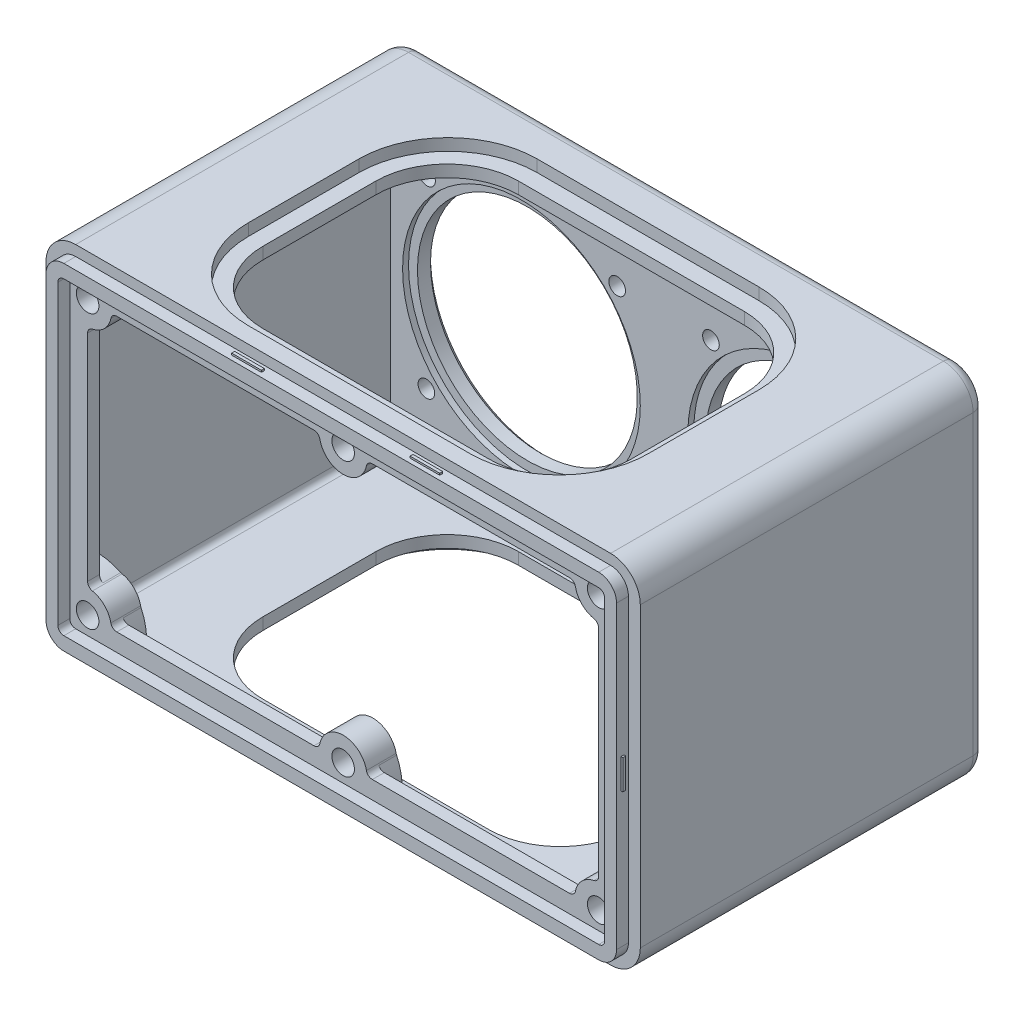
SolidWorks part; units mm, degrees
ref_plane "前视基准面" through (0, 0, 0) normal (0, 0, 1) x (1, 0, 0)
ref_plane "上视基准面" through (0, 0, 0) normal (0, 1, 0) x (1, 0, 0)
ref_plane "右视基准面" through (0, 0, 0) normal (1, 0, 0) x (0, 0, -1)
other "Configuration Table"
sketch "草图1" plane through (0, 0, 0) normal (0, 0, 1) x (1, 0, 0)
  line L0 (0, 0.156) -> (-70, 0.156) construction
  line L6 (-50, 30) -> (50, 30)
  line L11 (-50, 30) -> (-50, -30)
  line L12 (-50, -30) -> (50, -30)
  line L13 (50, 30) -> (50, -30)
  line L22 (-50, 30) -> (50, -30) construction
  line L23 (-50, -30) -> (50, 30) construction
  point P0 (0, 0)
  point P1 (0, 0)
  point P18 (0, 0)
  point P41 (0, 0)
  dimension "D1" = 100
  dimension "D2" = 60
extrude "凸台-拉伸2" add sketch "草图1" along normal blind 60
fillet "圆角1" radius 5 4 edges at (50, -30, 30) (50, 30, 30) (-50, 30, 30) (-50, -30, 30)
shell "抽壳2" thickness 4 removed face at (0, 0, 60)
fillet "圆角3" radius 2 8 edges at (48.5355, 28.5355, 0) (50, 0, 0) (48.5355, -28.5355, 0) (0, -30, 0) (-48.5355, -28.5355, 0) (-50, 0, 0) (-48.5355, 28.5355, 0) (0, 30, 0)
sketch "草图2" plane through (0, 0, 0) normal (0, 0, -1) x (-1, 0, 0)
  line L0 (0, 0) -> (-48, 0) construction
  circle A0 centre (-24, 0) radius 18
  circle A1 centre (24, 0) radius 18.5
  dimension "D1" = 36
  dimension "D2" = 37
  dimension "D3" = 24
  dimension "D4" = 24
extrude "切除-拉伸1" cut sketch "草图2" against normal up to next
sketch "草图3" plane through (0, -30, 0) normal (0, -1, 0) x (1, 0, 0)
  line L0 (0, 0) -> (0, 60) construction
  line L1 (-45, 60) -> (45, 60) construction
  line L2 (45, 31) -> (-45, 31) construction
  line L3 (45, 2) -> (45, 60) construction
  line L4 (-45, 60) -> (-45, 2) construction
  line L6 (19, 52.5) -> (-19, 52.5)
  line L7 (31, 40.5) -> (31, 21.5)
  line L8 (19, 9.5) -> (-19, 9.5)
  line L9 (-31, 40.5) -> (-31, 21.5)
  line L10 (31, 52.5) -> (-31, 9.5) construction
  line L11 (31, 9.5) -> (-31, 52.5) construction
  arc A0 (19, 9.5) -> (31, 21.5) centre (19, 21.5) ccw
  arc A1 (-31, 21.5) -> (-19, 9.5) centre (-19, 21.5) ccw
  arc A2 (-31, 40.5) -> (-19, 52.5) centre (-19, 40.5) cw
  arc A3 (19, 52.5) -> (31, 40.5) centre (19, 40.5) cw
  point P11 (0, 31)
  dimension "D1" = 12
extrude "切除-拉伸2" cut sketch "草图3" against normal up to surface (60 mm away) up to face at (0, 30, 31)
sketch "草图4" plane through (0, -30, 0) normal (0, -1, 0) x (1, 0, 0)
  line L0 (-45, 2) -> (45, 2) construction
  line L2 (0, 60) -> (0, 2) construction
  line L3 (18.65, 55.3) -> (-18.65, 55.3)
  line L4 (33.65, 40.3) -> (33.65, 21.7)
  line L5 (18.65, 6.7) -> (-18.65, 6.7)
  line L6 (-33.65, 40.3) -> (-33.65, 21.7)
  line L7 (33.65, 55.3) -> (-33.65, 6.7) construction
  line L8 (33.65, 6.7) -> (-33.65, 55.3) construction
  line L9 (-45, 60) -> (45, 60) construction
  arc A0 (-18.65, 6.7) -> (-33.65, 21.7) centre (-18.65, 21.7) cw
  arc A1 (-33.65, 40.3) -> (-18.65, 55.3) centre (-18.65, 40.3) cw
  arc A2 (33.65, 21.7) -> (18.65, 6.7) centre (18.65, 21.7) cw
  arc A3 (18.65, 55.3) -> (33.65, 40.3) centre (18.65, 40.3) cw
  point P5 (0, 31)
  point P26 (0, 31)
  dimension "D1" = 15
  dimension "D2" = 48.6
  dimension "D3" = 67.3
extrude "切除-拉伸3" cut sketch "草图4" against normal blind 2
sketch "草图5" plane through (0, 30, 0) normal (0, 1, 0) x (1, 0, 0)
  line L0 (-33.65, -40.3) -> (-33.65, -21.7) construction
  line L1 (18.65, -6.7) -> (-18.65, -6.7) construction
  line L2 (18.65, -55.3) -> (-18.65, -55.3) construction
  line L3 (33.65, -40.3) -> (33.65, -21.7) construction
  line L4 (-33.65, -40.3) -> (-33.65, -21.7)
  line L5 (18.65, -6.7) -> (-18.65, -6.7)
  line L6 (18.65, -55.3) -> (-18.65, -55.3)
  line L7 (33.65, -40.3) -> (33.65, -21.7)
  arc A0 (-33.65, -40.3) -> (-18.65, -55.3) centre (-18.65, -40.3) ccw construction
  arc A1 (-18.65, -6.7) -> (-33.65, -21.7) centre (-18.65, -21.7) ccw construction
  arc A2 (18.65, -55.3) -> (33.65, -40.3) centre (18.65, -40.3) ccw construction
  arc A3 (33.65, -21.7) -> (18.65, -6.7) centre (18.65, -21.7) ccw construction
  arc A4 (-33.65, -40.3) -> (-18.65, -55.3) centre (-18.65, -40.3) ccw
  arc A5 (-18.65, -6.7) -> (-33.65, -21.7) centre (-18.65, -21.7) ccw
  arc A6 (18.65, -55.3) -> (33.65, -40.3) centre (18.65, -40.3) ccw
  arc A7 (33.65, -21.7) -> (18.65, -6.7) centre (18.65, -21.7) ccw
extrude "切除-拉伸4" cut sketch "草图5" against normal blind 2
sketch "草图6" plane through (0, 0, 0) normal (0, 0, -1) x (-1, 0, 0)
  line L1 (200000, 0) -> (-200048, 0) construction
  line L2 (-40, -15.5) -> (-8, -15.5) construction
  line L3 (-39.8873, 15.5) -> (-7.8873, 15.5) construction
  line L4 (0, 0) -> (0, -28) construction
  line L5 (-24, 0) -> (-24, -15.5) construction
  circle A0 centre (-39.8873, 15.5) radius 1.4
  circle A1 centre (-40, -15.5) radius 1.4
  circle A3 centre (-8, -15.5) radius 1.4
  circle A4 centre (-7.8873, 15.5) radius 1.4
  circle A8 centre (8, -15.5) radius 1.4
  circle A9 centre (40, -15.5) radius 1.4
  circle A10 centre (7.8873, 15.5) radius 1.4
  circle A11 centre (39.8873, 15.5) radius 1.4
  point P16 (-24, -15.5)
  dimension "D1" = 2.8
  dimension "D5" = 2.8
  dimension "D6" = 2.8
  dimension "D7" = 2.8
  dimension "D2" = 31
  dimension "D3" = 32
  dimension "D4" = 32
  dimension "D8" = 15.5
extrude "切除-拉伸5" cut sketch "草图6" against normal up to next
sketch "草图7" plane through (0, 0, 60) normal (0, 0, 1) x (1, 0, 0)
  line L1 (45, 28.25) -> (-45, 28.25)
  line L2 (48, 25.25) -> (48, -25.25)
  line L3 (45, -28.25) -> (-45, -28.25)
  line L4 (-48, 25.25) -> (-48, -25.25)
  line L5 (48, 28.25) -> (-48, -28.25) construction
  line L6 (48, -28.25) -> (-48, 28.25) construction
  arc A0 (45, -28.25) -> (48, -25.25) centre (45, -25.25) ccw
  arc A1 (-48, -25.25) -> (-45, -28.25) centre (-45, -25.25) ccw
  arc A2 (-45, 28.25) -> (-48, 25.25) centre (-45, 25.25) ccw
  arc A3 (45, 28.25) -> (48, 25.25) centre (45, 25.25) cw
  point P0 (0, 0)
  dimension "D3" = 3
  dimension "D1" = 56.5
  dimension "D2" = 96
extrude "切除-拉伸6" cut sketch "草图7" against normal blind 2 flip side to cut
sketch "草图8" plane through (0, -28.25, 0) normal (0, -1, 0) x (1, 0, 0)
  line L0 (-45, 58) -> (-45, 60) construction
  line L1 (-45, 59) -> (45, 59) construction
  line L2 (45, 58) -> (45, 60) construction
  line L4 (12.5, 59.25) -> (17.5, 59.25)
  line L5 (12.5, 59.25) -> (12.5, 58.75)
  line L6 (12.5, 58.75) -> (17.5, 58.75)
  line L7 (17.5, 59.25) -> (17.5, 58.75)
  line L8 (12.5, 59.25) -> (17.5, 58.75) construction
  line L9 (12.5, 58.75) -> (17.5, 59.25) construction
  line L22 (-17.5, 59.25) -> (-12.5, 59.25)
  line L23 (-17.5, 59.25) -> (-17.5, 58.75)
  line L24 (-17.5, 58.75) -> (-12.5, 58.75)
  line L25 (-12.5, 59.25) -> (-12.5, 58.75)
  line L26 (-17.5, 59.25) -> (-12.5, 58.75) construction
  line L27 (-17.5, 58.75) -> (-12.5, 59.25) construction
  point P6 (15, 59)
  point P12 (-15, 59)
  dimension "D1" = 30
  dimension "D2" = 0.5
  dimension "D3" = 5
  dimension "D4" = 60
extrude "凸台-拉伸3" add sketch "草图8" along normal blind 0.3
sketch "草图9" plane through (0, 28.25, 0) normal (0, 1, 0) x (1, 0, 0)
  line L0 (-17.5, -59.25) -> (-12.5, -59.25) construction
  line L1 (-12.5, -59.25) -> (-12.5, -58.75) construction
  line L2 (-17.5, -58.75) -> (-12.5, -58.75) construction
  line L3 (-17.5, -59.25) -> (-17.5, -58.75) construction
  line L4 (12.5, -59.25) -> (12.5, -58.75) construction
  line L5 (17.5, -59.25) -> (17.5, -58.75) construction
  line L6 (12.5, -58.75) -> (17.5, -58.75) construction
  line L7 (12.5, -59.25) -> (17.5, -59.25) construction
  line L8 (-17.5, -59.25) -> (-12.5, -59.25)
  line L9 (-12.5, -59.25) -> (-12.5, -58.75)
  line L10 (-17.5, -58.75) -> (-12.5, -58.75)
  line L11 (-17.5, -59.25) -> (-17.5, -58.75)
  line L12 (12.5, -59.25) -> (12.5, -58.75)
  line L13 (17.5, -59.25) -> (17.5, -58.75)
  line L14 (12.5, -58.75) -> (17.5, -58.75)
  line L15 (12.5, -59.25) -> (17.5, -59.25)
extrude "凸台-拉伸4" add sketch "草图9" along normal blind 0.3
sketch "草图10" plane through (48, 0, 0) normal (1, 0, 0) x (0, 0, -1)
  line L0 (-59, -25.25) -> (-59, 25.25) construction
  line L1 (-59.25, -2.5) -> (-58.75, -2.5)
  line L2 (-59.25, -2.5) -> (-59.25, 2.5)
  line L3 (-59.25, 2.5) -> (-58.75, 2.5)
  line L4 (-58.75, -2.5) -> (-58.75, 2.5)
  line L5 (-59.25, -2.5) -> (-58.75, 2.5) construction
  line L6 (-59.25, 2.5) -> (-58.75, -2.5) construction
  line L7 (-58, -25.25) -> (-60, -25.25) construction
  line L8 (-58, 25.25) -> (-60, 25.25) construction
  point P0 (-59, 0)
  point P11 (-59, 0)
extrude "凸台-拉伸5" add sketch "草图10" along normal blind 0.3
sketch "草图11" plane through (-48, 0, 0) normal (-1, 0, 0) x (0, 0, 1)
  line L0 (59.25, -2.5) -> (58.75, -2.5) construction
  line L1 (59.25, -2.5) -> (59.25, 2.5) construction
  line L2 (59.25, 2.5) -> (58.75, 2.5) construction
  line L3 (58.75, -2.5) -> (58.75, 2.5) construction
  line L4 (59.25, -2.5) -> (58.75, -2.5)
  line L5 (59.25, -2.5) -> (59.25, 2.5)
  line L6 (59.25, 2.5) -> (58.75, 2.5)
  line L7 (58.75, -2.5) -> (58.75, 2.5)
extrude "凸台-拉伸6" add sketch "草图11" along normal blind 0.3
sketch "草图12" plane through (0, 0, 0) normal (0, 0, -1) x (-1, 0, 0)
  line L6 (0, 0) -> (0, -28.25) construction
sketch "草图13" plane through (0, 0, 4) normal (0, 0, 1) x (1, 0, 0)
  line L0 (0, 200000) -> (0, -200028.25) construction
  line L1 (0, 200000) -> (0, -200028.25)
  circle A0 centre (24, 0) radius 20
  circle A1 centre (-24, 0) radius 20
  dimension "D1" = 40
extrude "切除-拉伸8" cut sketch "草图13" against normal blind 1
sketch "草图14" plane through (0, 0, 58) normal (0, 0, 1) x (1, 0, 0)
  line L0 (0, 200000) -> (0, -200028.25) construction
  line L1 (45, 26) -> (-45, 26)
  line L2 (46, 25) -> (46, -25)
  line L3 (45, -26) -> (-45, -26)
  line L4 (-46, 25) -> (-46, -25)
  line L5 (46, 26) -> (-46, -26) construction
  line L6 (46, -26) -> (-46, 26) construction
  line L10 (-200000, 0) -> (200048, 0) construction
  line L11 (-200000, 0) -> (200048, 0)
  line L12 (0, 200000) -> (0, -200028.25)
  line L13 (43, 23) -> (-43, 23)
  line L14 (43, 23) -> (43, -23)
  line L15 (43, -23) -> (-43, -23)
  line L16 (-43, 23) -> (-43, -23)
  line L17 (43, 23) -> (-43, -23) construction
  line L18 (43, -23) -> (-43, 23) construction
  circle A0 centre (43, 23) radius 1.9
  circle A1 centre (0, 23) radius 1.9
  arc A6 (-45, 26) -> (-46, 25) centre (-45, 25) ccw
  arc A7 (-46, -25) -> (-45, -26) centre (-45, -25) ccw
  arc A8 (45, -26) -> (46, -25) centre (45, -25) ccw
  arc A9 (45, 26) -> (46, 25) centre (45, 25) cw
  circle A10 centre (-43, 23) radius 1.9
  circle A11 centre (-43, -23) radius 1.9
  circle A12 centre (0, -23) radius 1.9
  circle A13 centre (43, -23) radius 1.9
  circle A14 centre (43, 23) radius 4
  circle A15 centre (0, 23) radius 4
  circle A16 centre (-43, 23) radius 4
  circle A17 centre (-43, -23) radius 4
  circle A18 centre (0, -23) radius 4
  circle A19 centre (43, -23) radius 4
  point P0 (0, 0)
  point P5 (0, 0)
  point P23 (0, 0)
  dimension "D5" = 3
  dimension "D3" = 3.8
  dimension "D6" = 3.8
  dimension "D8" = 1
  dimension "D9" = 8
  dimension "D10" = 8
  dimension "D1" = 52
  dimension "D2" = 92
  dimension "D4" = 3
  dimension "D7" = 3
sketch "草图16" plane through (0, 0, 58) normal (0, 0, 1) x (1, 0, 0)
  line L0 (45, 26) -> (-45, 26) construction
  line L1 (-46, 25) -> (-46, -25) construction
  line L2 (46, 25) -> (46, -25) construction
  line L3 (45, -26) -> (-45, -26) construction
  line L4 (43, 23) -> (-43, 23) construction
  line L5 (43, 23) -> (43, -23) construction
  line L6 (43, -23) -> (-43, -23) construction
  line L7 (-43, 23) -> (-43, -23) construction
  line L8 (45, 26) -> (-45, 26)
  line L9 (-46, 25) -> (-46, -25)
  line L10 (46, 25) -> (46, -25)
  line L11 (45, -26) -> (-45, -26)
  line L12 (38.0883, 23) -> (4.9117, 23)
  line L13 (43, 18.0883) -> (43, -18.0883)
  line L14 (38.0883, -23) -> (4.9117, -23)
  line L15 (-43, 18.0883) -> (-43, -18.0883)
  line L16 (-4.9117, 23) -> (-38.0883, 23)
  line L17 (-4.9117, -23) -> (-38.0883, -23)
  arc A0 (-46, -25) -> (-45, -26) centre (-45, -25) ccw construction
  arc A1 (-45, 26) -> (-46, 25) centre (-45, 25) ccw construction
  arc A2 (46, 25) -> (45, 26) centre (45, 25) ccw construction
  arc A3 (45, -26) -> (46, -25) centre (45, -25) ccw construction
  circle A4 centre (43, -23) radius 4 construction
  circle A5 centre (43, 23) radius 4 construction
  circle A6 centre (-43, -23) radius 4 construction
  circle A7 centre (-43, 23) radius 4 construction
  arc A8 (-46, -25) -> (-45, -26) centre (-45, -25) ccw
  arc A9 (-45, 26) -> (-46, 25) centre (-45, 25) ccw
  arc A10 (46, 25) -> (45, 26) centre (45, 25) ccw
  arc A11 (45, -26) -> (46, -25) centre (45, -25) ccw
  arc A12 (42.19, -19.0829) -> (39.0829, -22.19) centre (43, -23) ccw
  arc A13 (39.0829, 22.19) -> (42.19, 19.0829) centre (43, 23) ccw
  arc A14 (-39.0829, -22.19) -> (-42.19, -19.0829) centre (-43, -23) ccw
  arc A15 (-42.19, 19.0829) -> (-39.0829, 22.19) centre (-43, 23) ccw
  arc A16 (-38.0883, -23) -> (-39.0829, -22.19) centre (-38.0883, -21.9844) cw
  arc A17 (-43, -18.0883) -> (-42.19, -19.0829) centre (-41.9844, -18.0883) ccw
  arc A18 (-43, 18.0883) -> (-42.19, 19.0829) centre (-41.9844, 18.0883) cw
  arc A19 (-39.0829, 22.19) -> (-38.0883, 23) centre (-38.0883, 21.9844) cw
  arc A20 (38.0883, -23) -> (39.0829, -22.19) centre (38.0883, -21.9844) ccw
  arc A21 (42.19, -19.0829) -> (43, -18.0883) centre (41.9844, -18.0883) ccw
  arc A22 (38.0883, 23) -> (39.0829, 22.19) centre (38.0883, 21.9844) cw
  arc A23 (42.19, 19.0829) -> (43, 18.0883) centre (41.9844, 18.0883) cw
  circle A24 centre (0, -23) radius 4 construction
  circle A25 centre (0, 23) radius 4 construction
  arc A26 (3.9171, -22.19) -> (-3.9171, -22.19) centre (0, -23) ccw
  arc A27 (-3.9171, 22.19) -> (3.9171, 22.19) centre (0, 23) ccw
  arc A28 (-4.9117, -23) -> (-3.9171, -22.19) centre (-4.9117, -21.9844) ccw
  arc A29 (4.9117, -23) -> (3.9171, -22.19) centre (4.9117, -21.9844) cw
  arc A30 (-4.9117, 23) -> (-3.9171, 22.19) centre (-4.9117, 21.9844) cw
  arc A31 (4.9117, 23) -> (3.9171, 22.19) centre (4.9117, 21.9844) ccw
  point P58 (-4, -23)
  point P63 (-4, 23)
  dimension "D1" = 1.0156
  dimension "D2" = 1.0156
extrude "凸台-拉伸7" add sketch "草图16" against normal blind 2
sketch "草图19" plane through (0, 0, 56) normal (0, 0, -1) x (-1, 0, 0)
  line L0 (-43, 23) -> (-43, -23) construction
  line L1 (-43, -23) -> (43, -23) construction
  line L2 (43, 23) -> (43, -23) construction
  line L3 (-43, 23) -> (43, 23) construction
  line L4 (-43, 23) -> (-43, 18.0883)
  line L5 (-43, -23) -> (-38.0883, -23)
  line L6 (43, 23) -> (43, 18.0883)
  line L7 (-43, 23) -> (-38.0883, 23)
  line L8 (-4.9117, -23) -> (4.9117, -23)
  line L9 (-43, -18.0883) -> (-43, -23)
  line L10 (-4.9117, 23) -> (4.9117, 23)
  line L11 (38.0883, -23) -> (43, -23)
  line L12 (43, -18.0883) -> (43, -23)
  line L13 (38.0883, 23) -> (43, 23)
  arc A0 (39.0829, 22.19) -> (38.0883, 23) centre (38.0883, 21.9844) ccw construction
  arc A1 (43, 18.0883) -> (42.19, 19.0829) centre (41.9844, 18.0883) ccw construction
  arc A2 (42.19, -19.0829) -> (43, -18.0883) centre (41.9844, -18.0883) ccw construction
  arc A3 (38.0883, -23) -> (39.0829, -22.19) centre (38.0883, -21.9844) ccw construction
  arc A4 (-4.9117, -23) -> (-3.9171, -22.19) centre (-4.9117, -21.9844) ccw construction
  arc A5 (3.9171, -22.19) -> (4.9117, -23) centre (4.9117, -21.9844) ccw construction
  arc A6 (-43, -18.0883) -> (-42.19, -19.0829) centre (-41.9844, -18.0883) ccw construction
  arc A7 (-39.0829, -22.19) -> (-38.0883, -23) centre (-38.0883, -21.9844) ccw construction
  arc A8 (-38.0883, 23) -> (-39.0829, 22.19) centre (-38.0883, 21.9844) ccw construction
  arc A9 (-42.19, 19.0829) -> (-43, 18.0883) centre (-41.9844, 18.0883) ccw construction
  arc A10 (-3.9171, 22.19) -> (-4.9117, 23) centre (-4.9117, 21.9844) ccw construction
  circle A12 centre (43, 23) radius 4 construction
  circle A13 centre (43, -23) radius 4 construction
  circle A14 centre (0, -23) radius 4 construction
  circle A15 centre (-43, -23) radius 4 construction
  circle A16 centre (-43, 23) radius 4 construction
  arc A17 (39.0829, 22.19) -> (38.0883, 23) centre (38.0883, 21.9844) ccw
  arc A18 (43, 18.0883) -> (42.19, 19.0829) centre (41.9844, 18.0883) ccw
  arc A19 (42.19, -19.0829) -> (43, -18.0883) centre (41.9844, -18.0883) ccw
  arc A20 (38.0883, -23) -> (39.0829, -22.19) centre (38.0883, -21.9844) ccw
  arc A21 (-4.9117, -23) -> (-3.9171, -22.19) centre (-4.9117, -21.9844) ccw
  arc A22 (3.9171, -22.19) -> (4.9117, -23) centre (4.9117, -21.9844) ccw
  arc A23 (-43, -18.0883) -> (-42.19, -19.0829) centre (-41.9844, -18.0883) ccw
  arc A24 (-39.0829, -22.19) -> (-38.0883, -23) centre (-38.0883, -21.9844) ccw
  arc A25 (-38.0883, 23) -> (-39.0829, 22.19) centre (-38.0883, 21.9844) ccw
  arc A26 (-42.19, 19.0829) -> (-43, 18.0883) centre (-41.9844, 18.0883) ccw
  arc A27 (-3.9171, 22.19) -> (-4.9117, 23) centre (-4.9117, 21.9844) ccw
  arc A29 (39.0829, 22.19) -> (42.19, 19.0829) centre (43, 23) ccw
  arc A30 (42.19, -19.0829) -> (39.0829, -22.19) centre (43, -23) ccw
  arc A31 (3.9171, -22.19) -> (-3.9171, -22.19) centre (0, -23) ccw
  arc A32 (-39.0829, -22.19) -> (-42.19, -19.0829) centre (-43, -23) ccw
  arc A33 (-42.19, 19.0829) -> (-39.0829, 22.19) centre (-43, 23) ccw
  arc A34 (4.9117, 23) -> (3.9171, 22.19) centre (4.9117, 21.9844) ccw construction
  circle A35 centre (0, 23) radius 4 construction
  arc A36 (4.9117, 23) -> (3.9171, 22.19) centre (4.9117, 21.9844) ccw
  arc A37 (-3.9171, 22.19) -> (3.9171, 22.19) centre (0, 23) ccw
sketch "草图20" plane through (0, 0, 56) normal (0, 0, -1) x (-1, 0, 0)
  line L4 (-38.0883, 23) -> (-38.0883, 26)
  line L5 (-45, 26) -> (45, 26) construction
  line L6 (-43, 18.0883) -> (-46, 18.0883)
  line L7 (-46, -25) -> (-46, 25) construction
  line L8 (-46, -25) -> (-46, 25) construction
  line L9 (-45, 26) -> (-38.0883, 26)
  line L10 (-46, 18.0883) -> (-46, 25)
  line L11 (43, -18.0883) -> (46, -18.0883)
  line L12 (46, 25) -> (46, -25) construction
  line L13 (38.0883, -23) -> (38.0883, -26)
  line L14 (45, -26) -> (-45, -26) construction
  line L16 (-4.9117, -23) -> (-4.9117, -26)
  line L17 (4.9117, -23) -> (4.9117, -26)
  line L18 (4.9117, 23) -> (4.9117, 26)
  line L19 (-45, 26) -> (45, 26) construction
  line L20 (-4.9117, 23) -> (-4.9117, 26)
  line L21 (43, 18.0883) -> (46, 18.0883)
  line L22 (46, 25) -> (46, -25) construction
  line L23 (38.0883, 23) -> (38.0883, 26)
  line L24 (-38.0883, -23) -> (-38.0883, -26)
  line L25 (-43, -18.0883) -> (-46, -18.0883)
  line L26 (-46, -25) -> (-46, -18.0883)
  line L27 (-45, 26) -> (-38.0883, 26)
  line L28 (45, -26) -> (38.0883, -26)
  line L29 (46, 25) -> (46, 18.0883)
  line L30 (-46, 18.0883) -> (-46, 25)
  line L31 (-38.0883, -26) -> (-45, -26)
  line L32 (4.9117, -26) -> (-4.9117, -26)
  line L33 (-4.9117, 26) -> (4.9117, 26)
  line L34 (38.0883, 26) -> (45, 26)
  line L35 (46, -18.0883) -> (46, -25)
  arc A0 (-42.19, 19.0829) -> (-43, 18.0883) centre (-41.9844, 18.0883) ccw construction
  arc A1 (-42.19, 19.0829) -> (-39.0829, 22.19) centre (-43, 23) ccw construction
  arc A2 (-38.0883, 23) -> (-39.0829, 22.19) centre (-38.0883, 21.9844) ccw construction
  arc A3 (-42.19, 19.0829) -> (-43, 18.0883) centre (-41.9844, 18.0883) ccw
  arc A4 (-42.19, 19.0829) -> (-39.0829, 22.19) centre (-43, 23) ccw
  arc A5 (-38.0883, 23) -> (-39.0829, 22.19) centre (-38.0883, 21.9844) ccw
  arc A6 (-45, 26) -> (-46, 25) centre (-45, 25) ccw construction
  arc A7 (-45, 26) -> (-46, 25) centre (-45, 25) ccw
  arc A8 (43, 18.0883) -> (42.19, 19.0829) centre (41.9844, 18.0883) ccw construction
  arc A9 (39.0829, 22.19) -> (42.19, 19.0829) centre (43, 23) ccw construction
  arc A10 (39.0829, 22.19) -> (38.0883, 23) centre (38.0883, 21.9844) ccw construction
  arc A11 (38.0883, -23) -> (39.0829, -22.19) centre (38.0883, -21.9844) ccw construction
  arc A12 (42.19, -19.0829) -> (39.0829, -22.19) centre (43, -23) ccw construction
  arc A13 (42.19, -19.0829) -> (43, -18.0883) centre (41.9844, -18.0883) ccw construction
  arc A14 (4.9117, 23) -> (3.9171, 22.19) centre (4.9117, 21.9844) ccw construction
  arc A15 (-3.9171, 22.19) -> (3.9171, 22.19) centre (0, 23) ccw construction
  arc A16 (-3.9171, 22.19) -> (-4.9117, 23) centre (-4.9117, 21.9844) ccw construction
  arc A17 (3.9171, -22.19) -> (4.9117, -23) centre (4.9117, -21.9844) ccw construction
  arc A18 (3.9171, -22.19) -> (-3.9171, -22.19) centre (0, -23) ccw construction
  arc A19 (-4.9117, -23) -> (-3.9171, -22.19) centre (-4.9117, -21.9844) ccw construction
  arc A20 (-43, -18.0883) -> (-42.19, -19.0829) centre (-41.9844, -18.0883) ccw construction
  arc A21 (-39.0829, -22.19) -> (-42.19, -19.0829) centre (-43, -23) ccw construction
  arc A22 (-39.0829, -22.19) -> (-38.0883, -23) centre (-38.0883, -21.9844) ccw construction
  arc A23 (43, 18.0883) -> (42.19, 19.0829) centre (41.9844, 18.0883) ccw
  arc A24 (39.0829, 22.19) -> (42.19, 19.0829) centre (43, 23) ccw
  arc A25 (39.0829, 22.19) -> (38.0883, 23) centre (38.0883, 21.9844) ccw
  arc A26 (38.0883, -23) -> (39.0829, -22.19) centre (38.0883, -21.9844) ccw
  arc A27 (42.19, -19.0829) -> (39.0829, -22.19) centre (43, -23) ccw
  arc A28 (42.19, -19.0829) -> (43, -18.0883) centre (41.9844, -18.0883) ccw
  arc A29 (4.9117, 23) -> (3.9171, 22.19) centre (4.9117, 21.9844) ccw
  arc A30 (-3.9171, 22.19) -> (3.9171, 22.19) centre (0, 23) ccw
  arc A31 (-3.9171, 22.19) -> (-4.9117, 23) centre (-4.9117, 21.9844) ccw
  arc A32 (3.9171, -22.19) -> (4.9117, -23) centre (4.9117, -21.9844) ccw
  arc A33 (3.9171, -22.19) -> (-3.9171, -22.19) centre (0, -23) ccw
  arc A34 (-4.9117, -23) -> (-3.9171, -22.19) centre (-4.9117, -21.9844) ccw
  arc A35 (-43, -18.0883) -> (-42.19, -19.0829) centre (-41.9844, -18.0883) ccw
  arc A36 (-39.0829, -22.19) -> (-42.19, -19.0829) centre (-43, -23) ccw
  arc A37 (-39.0829, -22.19) -> (-38.0883, -23) centre (-38.0883, -21.9844) ccw
  arc A38 (-46, -25) -> (-45, -26) centre (-45, -25) ccw construction
  arc A39 (46, 25) -> (45, 26) centre (45, 25) ccw construction
  arc A40 (45, -26) -> (46, -25) centre (45, -25) ccw construction
  arc A41 (-46, -25) -> (-45, -26) centre (-45, -25) ccw
  arc A42 (46, 25) -> (45, 26) centre (45, 25) ccw
  arc A43 (45, -26) -> (46, -25) centre (45, -25) ccw
sketch "草图21" plane through (0, 0, 56) normal (0, 0, -1) x (-1, 0, 0)
  line L0 (45, -26) -> (38.0883, -26) construction
  line L1 (46, -18.0883) -> (46, -25) construction
  line L2 (43, -18.0883) -> (46, -18.0883) construction
  line L3 (38.0883, -23) -> (38.0883, -26) construction
  line L4 (45, -26) -> (38.0883, -26)
  line L5 (46, -18.0883) -> (46, -25)
  line L6 (43, -18.0883) -> (46, -18.0883)
  line L7 (38.0883, -23) -> (38.0883, -26)
  line L8 (200000, 0) -> (-200048, 0) construction
  line L9 (0, 200000) -> (0, -200028.25) construction
  line L10 (200000, 0) -> (-200048, 0)
  line L11 (0, 200000) -> (0, -200028.25)
  arc A0 (45, -26) -> (46, -25) centre (45, -25) ccw construction
  arc A1 (42.19, -19.0829) -> (43, -18.0883) centre (41.9844, -18.0883) ccw construction
  arc A2 (42.19, -19.0829) -> (39.0829, -22.19) centre (43, -23) ccw construction
  arc A3 (38.0883, -23) -> (39.0829, -22.19) centre (38.0883, -21.9844) ccw construction
  arc A4 (45, -26) -> (46, -25) centre (45, -25) ccw
  arc A5 (42.19, -19.0829) -> (43, -18.0883) centre (41.9844, -18.0883) ccw
  arc A6 (42.19, -19.0829) -> (39.0829, -22.19) centre (43, -23) ccw
  arc A7 (38.0883, -23) -> (39.0829, -22.19) centre (38.0883, -21.9844) ccw
extrude "凸台-拉伸10" add sketch "草图21" along normal blind 3
sketch "草图22" plane through (0, 0, 56) normal (0, 0, -1) x (-1, 0, 0)
  line L0 (4.9117, -23) -> (4.9117, -26) construction
  line L1 (4.9117, -26) -> (-4.9117, -26) construction
  line L2 (-4.9117, -23) -> (-4.9117, -26) construction
  line L3 (4.9117, -23) -> (4.9117, -26)
  line L4 (4.9117, -26) -> (-4.9117, -26)
  line L5 (-4.9117, -23) -> (-4.9117, -26)
  arc A0 (-4.9117, -23) -> (-3.9171, -22.19) centre (-4.9117, -21.9844) ccw construction
  arc A1 (3.9171, -22.19) -> (-3.9171, -22.19) centre (0, -23) ccw construction
  arc A2 (3.9171, -22.19) -> (4.9117, -23) centre (4.9117, -21.9844) ccw construction
  arc A3 (-4.9117, -23) -> (-3.9171, -22.19) centre (-4.9117, -21.9844) ccw
  arc A4 (3.9171, -22.19) -> (-3.9171, -22.19) centre (0, -23) ccw
  arc A5 (3.9171, -22.19) -> (4.9117, -23) centre (4.9117, -21.9844) ccw
extrude "凸台-拉伸11" add sketch "草图22" along normal blind 3
sketch "草图23" plane through (0, 0, 56) normal (0, 0, -1) x (-1, 0, 0)
  line L0 (-38.0883, -26) -> (-45, -26) construction
  line L1 (-46, -25) -> (-46, -18.0883) construction
  line L2 (-43, -18.0883) -> (-46, -18.0883) construction
  line L3 (-38.0883, -23) -> (-38.0883, -26) construction
  line L4 (-38.0883, -26) -> (-45, -26)
  line L5 (-46, -25) -> (-46, -18.0883)
  line L6 (-43, -18.0883) -> (-46, -18.0883)
  line L7 (-38.0883, -23) -> (-38.0883, -26)
  arc A0 (-46, -25) -> (-45, -26) centre (-45, -25) ccw construction
  arc A1 (-43, -18.0883) -> (-42.19, -19.0829) centre (-41.9844, -18.0883) ccw construction
  arc A2 (-39.0829, -22.19) -> (-42.19, -19.0829) centre (-43, -23) ccw construction
  arc A3 (-39.0829, -22.19) -> (-38.0883, -23) centre (-38.0883, -21.9844) ccw construction
  arc A4 (-46, -25) -> (-45, -26) centre (-45, -25) ccw
  arc A5 (-43, -18.0883) -> (-42.19, -19.0829) centre (-41.9844, -18.0883) ccw
  arc A6 (-39.0829, -22.19) -> (-42.19, -19.0829) centre (-43, -23) ccw
  arc A7 (-39.0829, -22.19) -> (-38.0883, -23) centre (-38.0883, -21.9844) ccw
extrude "凸台-拉伸12" add sketch "草图23" along normal blind 3
sketch "草图24" plane through (0, 0, 56) normal (0, 0, -1) x (-1, 0, 0)
  line L0 (-43, 18.0883) -> (-46, 18.0883) construction
  line L1 (-46, 18.0883) -> (-46, 25) construction
  line L2 (-45, 26) -> (-38.0883, 26) construction
  line L3 (-38.0883, 23) -> (-38.0883, 26) construction
  line L4 (-43, 18.0883) -> (-46, 18.0883)
  line L5 (-46, 18.0883) -> (-46, 25)
  line L6 (-45, 26) -> (-38.0883, 26)
  line L7 (-38.0883, 23) -> (-38.0883, 26)
  arc A0 (-42.19, 19.0829) -> (-43, 18.0883) centre (-41.9844, 18.0883) ccw construction
  arc A1 (-45, 26) -> (-46, 25) centre (-45, 25) ccw construction
  arc A2 (-38.0883, 23) -> (-39.0829, 22.19) centre (-38.0883, 21.9844) ccw construction
  arc A3 (-42.19, 19.0829) -> (-39.0829, 22.19) centre (-43, 23) ccw construction
  arc A4 (-42.19, 19.0829) -> (-43, 18.0883) centre (-41.9844, 18.0883) ccw
  arc A5 (-45, 26) -> (-46, 25) centre (-45, 25) ccw
  arc A6 (-38.0883, 23) -> (-39.0829, 22.19) centre (-38.0883, 21.9844) ccw
  arc A7 (-42.19, 19.0829) -> (-39.0829, 22.19) centre (-43, 23) ccw
extrude "凸台-拉伸13" add sketch "草图24" along normal blind 3
sketch "草图26" plane through (0, 0, 56) normal (0, 0, -1) x (-1, 0, 0)
  line L0 (4.9117, 23) -> (4.9117, 26) construction
  line L1 (-4.9117, 26) -> (4.9117, 26) construction
  line L2 (-4.9117, 23) -> (-4.9117, 26) construction
  line L3 (4.9117, 23) -> (4.9117, 26)
  line L4 (-4.9117, 26) -> (4.9117, 26)
  line L5 (-4.9117, 23) -> (-4.9117, 26)
  arc A0 (-3.9171, 22.19) -> (-4.9117, 23) centre (-4.9117, 21.9844) ccw construction
  arc A1 (-3.9171, 22.19) -> (3.9171, 22.19) centre (0, 23) ccw construction
  arc A2 (4.9117, 23) -> (3.9171, 22.19) centre (4.9117, 21.9844) ccw construction
  arc A3 (-3.9171, 22.19) -> (-4.9117, 23) centre (-4.9117, 21.9844) ccw
  arc A4 (-3.9171, 22.19) -> (3.9171, 22.19) centre (0, 23) ccw
  arc A5 (4.9117, 23) -> (3.9171, 22.19) centre (4.9117, 21.9844) ccw
extrude "凸台-拉伸14" add sketch "草图26" along normal blind 3
sketch "草图27" plane through (0, 0, 56) normal (0, 0, -1) x (-1, 0, 0)
  line L0 (38.0883, 26) -> (45, 26) construction
  line L1 (38.0883, 23) -> (38.0883, 26) construction
  line L2 (43, 18.0883) -> (46, 18.0883) construction
  line L3 (46, 25) -> (46, 18.0883) construction
  line L4 (38.0883, 26) -> (45, 26)
  line L5 (38.0883, 23) -> (38.0883, 26)
  line L6 (43, 18.0883) -> (46, 18.0883)
  line L7 (46, 25) -> (46, 18.0883)
  arc A0 (46, 25) -> (45, 26) centre (45, 25) ccw construction
  arc A1 (39.0829, 22.19) -> (38.0883, 23) centre (38.0883, 21.9844) ccw construction
  arc A2 (39.0829, 22.19) -> (42.19, 19.0829) centre (43, 23) ccw construction
  arc A3 (43, 18.0883) -> (42.19, 19.0829) centre (41.9844, 18.0883) ccw construction
  arc A4 (46, 25) -> (45, 26) centre (45, 25) ccw
  arc A5 (39.0829, 22.19) -> (38.0883, 23) centre (38.0883, 21.9844) ccw
  arc A6 (39.0829, 22.19) -> (42.19, 19.0829) centre (43, 23) ccw
  arc A7 (43, 18.0883) -> (42.19, 19.0829) centre (41.9844, 18.0883) ccw
extrude "凸台-拉伸15" add sketch "草图27" along normal blind 3
fillet "圆角4" radius 10 12 edges at (38.0883, 23, 54.5) (43, 18.0883, 54.5) (43, -18.0883, 54.5) (38.0883, -23, 54.5) (-4.9117, -23, 54.5) (4.9117, -23, 54.5) (-43, -18.0883, 54.5) (-38.0883, -23, 54.5) (-38.0883, 23, 54.5) (-43, 18.0883, 54.5) (-4.9117, 23, 54.5) (4.9117, 23, 54.5)
sketch "草图28" plane through (0, 0, 58) normal (0, 0, 1) x (1, 0, 0)
  circle A0 centre (43, -23) radius 1.9 construction
  circle A1 centre (43, 23) radius 1.9 construction
  circle A2 centre (0, 23) radius 1.9 construction
  circle A3 centre (0, -23) radius 1.9 construction
  circle A4 centre (-43, 23) radius 1.9 construction
  circle A5 centre (-43, -23) radius 1.9 construction
  circle A6 centre (43, -23) radius 1.9
  circle A7 centre (43, 23) radius 1.9
  circle A8 centre (0, 23) radius 1.9
  circle A9 centre (0, -23) radius 1.9
  circle A10 centre (-43, 23) radius 1.9
  circle A11 centre (-43, -23) radius 1.9
extrude "切除-拉伸9" cut sketch "草图28" against normal up to next
chamfer "倒角1" distance 0.8 angle 45 2 edges at (-42.5, 0, 0) (6, 0, 0)
